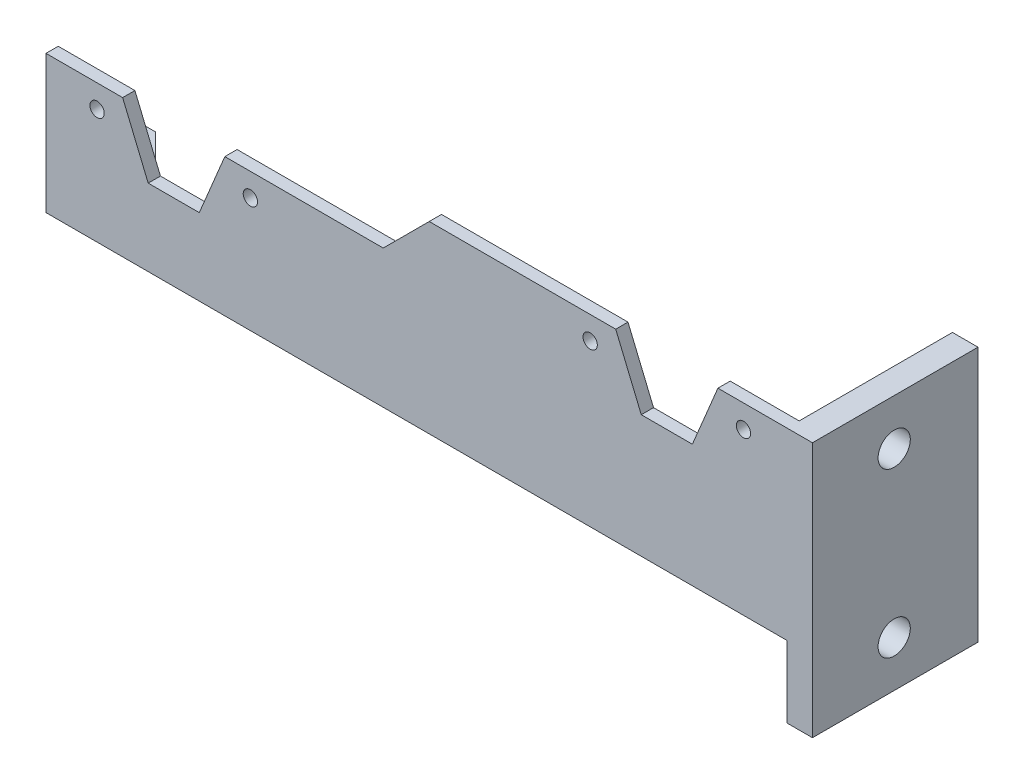
SolidWorks part; units mm, degrees
ref_plane "Front Plane" through (0, 0, 0) normal (0, 0, 1) x (1, 0, 0)
ref_plane "Top Plane" through (0, 0, 0) normal (0, 1, 0) x (1, 0, 0)
ref_plane "Right Plane" through (0, 0, 0) normal (1, 0, 0) x (0, 0, -1)
sketch "Sketch1" plane through (0, 0, 0) normal (0, 0, 1) x (1, 0, 0)
  line L1 (0, 0) -> (150, 0)
  line L2 (0, 0) -> (0, 36)
  line L3 (0, 36) -> (150, 36)
  line L4 (150, 0) -> (150, 36)
  dimension "D1" = 150
  dimension "D2" = 36
extrude "Boss-Extrude1" add sketch "Sketch1" along normal blind 2.4
sketch "Sketch10" plane through (0, 0, 2.4) normal (0, 0, 1) x (1, 0, 0)
  line L1 (0, 36) -> (75, 36)
  line L2 (0, 36) -> (0, 27)
  line L3 (0, 27) -> (75, 27)
  line L4 (75, 36) -> (75, 27)
  dimension "D1" = 9
extrude "Cut-Extrude5" cut sketch "Sketch10" against normal blind 10
sketch "Sketch2" plane through (0, 0, 2.4) normal (0, 0, 1) x (1, 0, 0)
  line L0 (25, 36) -> (25, 0) construction
  line L1 (150, 36) -> (75, 36) construction
  line L2 (0, 0) -> (150, 0) construction
  line L3 (121.5, 36) -> (121.5, 0) construction
  line L4 (150, 0) -> (150, 36) construction
  line L5 (131.5, 36) -> (126.5, 24)
  line L6 (126.5, 24) -> (116.5, 24)
  line L7 (111.5, 36) -> (116.5, 24)
  line L8 (35, 27) -> (30, 15)
  line L9 (30, 15) -> (20, 15)
  line L10 (15, 27) -> (20, 15)
  line L11 (15, 27) -> (35, 27)
  line L12 (111.5, 36) -> (131.5, 36)
  line L15 (73.25, 36) -> (73.25, 0) construction
  line L16 (0, 27) -> (75, 27) construction
  circle A0 centre (40, 22.5) radius 1.4
  circle A1 centre (10, 22.5) radius 1.4
  circle A2 centre (106.5, 31.5) radius 1.4
  circle A3 centre (136.5, 31.5) radius 1.4
  point P14 (121.5, 24)
  point P19 (25, 15)
  dimension "D10" = 2.8
  dimension "D2" = 125
  dimension "D3" = 5
  dimension "D5" = 5
  dimension "D6" = 10
  dimension "D7" = 12
  dimension "D8" = 12
  dimension "D9" = 4.5
  dimension "D11" = 15
  dimension "D12" = 48.25
  dimension "D13" = 4.5
extrude "Cut-Extrude1" cut sketch "Sketch2" against normal through all
chamfer "Chamfer6" distance 9 angle 45 1 edges at (75, 27, 1.2)
sketch "Sketch3" plane through (0, 0, 0) normal (0, 0, -1) x (-1, 0, 0)
  line L1 (-150, 36) -> (-145, 36)
  line L2 (-150, 36) -> (-150, -14)
  line L3 (-150, -14) -> (-145, -14)
  line L4 (-145, 36) -> (-145, -14)
  line L5 (-150, 36) -> (-131.5, 36) construction
  line L6 (0, 0) -> (-150, 0) construction
  dimension "D1" = 5
  dimension "D2" = 50
extrude "Boss-Extrude2" add sketch "Sketch3" along normal blind 30 and the other way up to surface (2.4 mm away) other way up to face at (137.9, 31.5, 2.4)
sketch "Sketch4" plane through (145, 0, 0) normal (-1, 0, 0) x (0, 0, 1)
  line L0 (-13.6, 36) -> (-13.6, -14) construction
  line L1 (-30, 36) -> (0, 36) construction
  line L2 (-30, -14) -> (2.4, -14) construction
  line L3 (2.4, -14) -> (2.4, 36) construction
  circle A0 centre (-13.6, 27) radius 3.15
  circle A1 centre (-13.6, -5) radius 3.15
  dimension "D2" = 6.3
  dimension "D4" = 6.3
  dimension "D1" = 16
  dimension "D3" = 9
  dimension "D5" = 9
extrude "Cut-Extrude2" cut sketch "Sketch4" against normal blind 30
sketch "Sketch6" plane through (0, 0, 0) normal (0, -1, 0) x (1, 0, 0)
  line L0 (145, -30) -> (145, 2.4) construction
  line L1 (0, 0) -> (145, 0)
  line L2 (0, 0) -> (0, -2)
  line L3 (0, -2) -> (145, -2)
  line L4 (145, 0) -> (145, -2)
  dimension "D1" = 2
extrude "Boss-Extrude3" [suppressed] add sketch "Sketch6" against normal up to surface (15 mm away)
sketch "Sketch7" [suppressed] plane through (0, 0, 0) normal (-1, 0, 0) x (0, 0, 1)
  line L0 (-2, 0) -> (0, 15)
  line L1 (0, 15) -> (-5.2606, 15)
  line L2 (-5.2606, 15) -> (-2, 0)
extrude "Cut-Extrude3" [suppressed] cut sketch "Sketch7" against normal up to surface (144 mm away)
chamfer "Chamfer2" [suppressed] distance 2 angle 45
fillet "Fillet2" [suppressed] radius 2
chamfer "Chamfer3" [suppressed] distance 3 angle 15
chamfer "Chamfer4" [suppressed] distance 2 angle 79
sketch "Sketch8" plane through (145, 0, 0) normal (-1, 0, 0) x (0, 0, 1)
  line L0 (-30, 11) -> (0, 11) construction
  line L1 (-30, -14) -> (-30, 36) construction
  line L2 (0, 0) -> (0, 36) construction
  line L4 (-10, 10) -> (0, 10)
  line L5 (-10, 10) -> (-10, 12)
  line L6 (-10, 12) -> (0, 12)
  line L7 (0, 10) -> (0, 12)
  line L8 (-10, 10) -> (0, 12) construction
  line L9 (-10, 12) -> (0, 10) construction
  point P6 (-5, 11)
  dimension "D1" = 2
  dimension "D2" = 10
extrude "Boss-Extrude4" add sketch "Sketch8" along normal up to surface (145 mm away) up to face at (0, 13.5, 1.2)
sketch "Sketch9" plane through (0, 36, 0) normal (0, 1, 0) x (1, 0, 0)
  line L0 (131.5, 0) -> (131.5, 12.5409)
  line L1 (131.5, 12.5409) -> (111.5, 12.5409)
  line L2 (111.5, 12.5409) -> (111.5, 0)
  line L3 (111.5, 0) -> (131.5, 0)
  line L4 (35, 0) -> (35, 13.0069)
  line L5 (35, 13.0069) -> (15, 13.0069)
  line L6 (15, 13.0069) -> (15, 0)
  line L7 (15, 0) -> (35, 0)
  point P10 (0, 0)
  point P13 (0, 0)
extrude "Cut-Extrude4" cut sketch "Sketch9" against normal through all
chamfer "Chamfer5" distance 6 angle 45 5 edges at (111.5, 11, -10) (15, 11, -10) (0, 11, -10) (35, 11, -10) (131.5, 11, -10)
